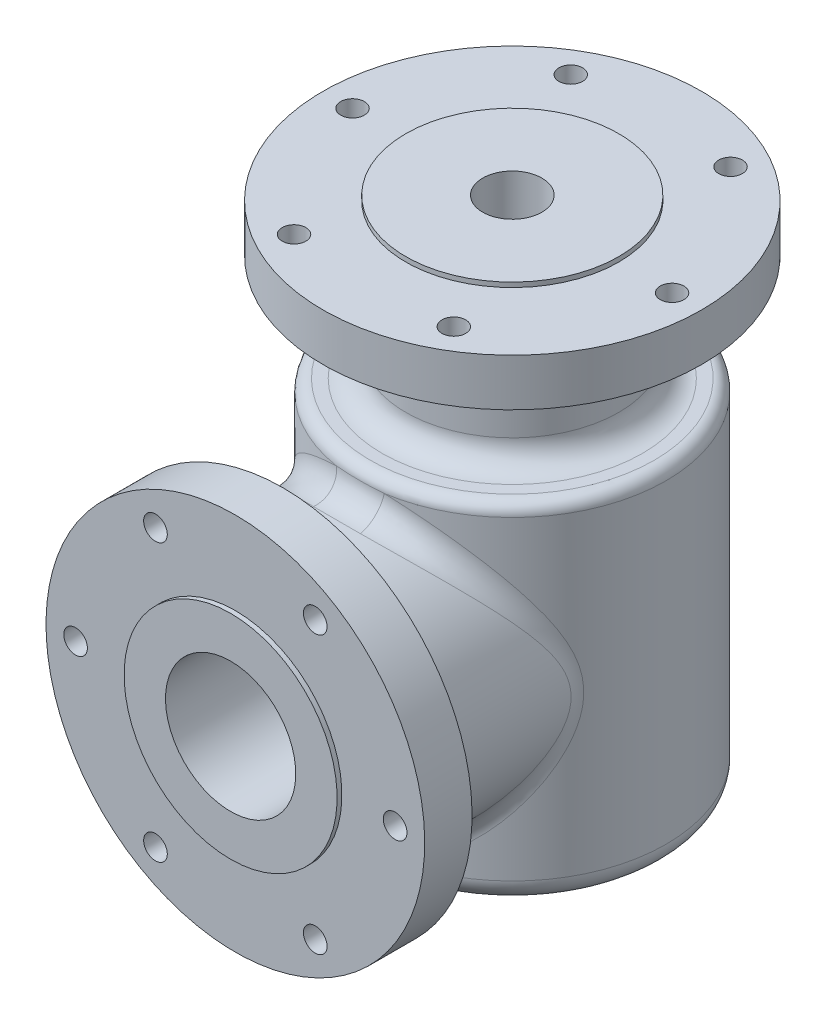
SolidWorks part; units mm, degrees
ref_plane "Front Plane" through (0, 0, 0) normal (0, 0, 1) x (1, 0, 0)
ref_plane "Top Plane" through (0, 0, 0) normal (0, 1, 0) x (1, 0, 0)
ref_plane "Right Plane" through (0, 0, 0) normal (1, 0, 0) x (0, 0, -1)
sketch "Sketch1" plane through (0, 0, 0) normal (0, 0, 1) x (1, 0, 0)
  line L0 (0, 0) -> (0, 259.5727) construction
  line L1 (21, 0) -> (55, 0)
  line L2 (65, 10) -> (65, 143)
  line L3 (60, 148) -> (55, 148)
  line L4 (45, 158) -> (45, 183)
  line L5 (55, 193) -> (80, 193)
  line L6 (80, 193) -> (80, 213)
  line L7 (80, 213) -> (45, 213)
  line L8 (45, 213) -> (45, 215)
  line L9 (45, 215) -> (12.5, 215)
  line L10 (15, 41.7864) -> (29, 41.7864)
  line L11 (43, 55.7864) -> (43, 115.7864)
  line L12 (29, 129.7864) -> (18, 129.7864)
  line L13 (12.5, 215) -> (12.5, 137.7864)
  line L14 (12.5, 137.7864) -> (18, 129.7864)
  line L15 (15, 41.7864) -> (15, 4)
  line L16 (15, 4) -> (21, 0)
  arc A0 (29, 41.7864) -> (43, 55.7864) centre (29, 55.7864) ccw
  arc A1 (43, 115.7864) -> (29, 129.7864) centre (29, 115.7864) ccw
  arc A2 (55, 148) -> (45, 158) centre (55, 158) cw
  arc A3 (45, 183) -> (55, 193) centre (55, 183) cw
  arc A4 (55, 0) -> (65, 10) centre (55, 10) ccw
  arc A5 (65, 143) -> (60, 148) centre (60, 143) ccw
  point P17 (0, 215)
  point P24 (43, 41.7864)
  point P27 (43, 129.7864)
  point P33 (65, 0)
  point P36 (65, 148)
  dimension "D18" = 14
  dimension "D19" = 10
  dimension "D20" = 10
  dimension "D21" = 5
  dimension "D1" = 65
  dimension "D2" = 215
  dimension "D3" = 148
  dimension "D4" = 88
  dimension "D5" = 21
  dimension "D6" = 43
  dimension "D7" = 2
  dimension "D8" = 15
  dimension "D9" = 4
  dimension "D10" = 37.7864
  dimension "D11" = 20
  dimension "D12" = 80
  dimension "D13" = 45
  dimension "D14" = 45
  dimension "D15" = 12.5
  dimension "D16" = 8
  dimension "D17" = 18
revolve "Revolve1" add sketch "Sketch1" angle 360 about L0
sketch "Sketch2" plane through (0, 0, 0) normal (1, 0, 0) x (0, 0, -1)
  line L0 (65, 76.5) -> (-119, 76.5) construction
  line L1 (65, 10) -> (65, 143) construction
  line L2 (-119, 104.0144) -> (-119, 121.5)
  line L3 (-119, 121.5) -> (-117, 121.5)
  line L4 (-117, 121.5) -> (-117, 156.5)
  line L5 (-117, 156.5) -> (-97, 156.5)
  line L6 (-97, 156.5) -> (-97, 134.0144)
  line L7 (-97, 134.0144) -> (-29.9513, 134.0144)
  line L8 (-29.9513, 134.0144) -> (-29.9513, 104.0144)
  line L9 (-119, 104.0144) -> (-29.9513, 104.0144)
  point P12 (-29.9513, 111.5)
  dimension "D1" = 45
  dimension "D2" = 80
  dimension "D3" = 2
  dimension "D4" = 20
  dimension "D5" = 57.5144
  dimension "D6" = 87.0487
  dimension "D7" = 30
  dimension "D8" = 94.9513
  dimension "D9" = 184
revolve "Revolve3" add sketch "Sketch2" angle 360 about L0
sketch "Sketch3" plane through (0, 0, 119) normal (0, 0, 1) x (1, 0, 0)
  circle A0 centre (0, 76.5) radius 27.5144
  dimension "D1" = 55.0287
extrude "Cut-Extrude1" cut sketch "Sketch3" against normal blind 119
fillet "Fillet1" radius 10 1 edges at (0, 134.0144, 97)
fillet "Fillet2" radius 10 1 edges at (5.3839, 19.2382, 64.7766)
sketch "Sketch4" plane through (0, 213, 0) normal (0, 1, 0) x (1, 0, 0)
  circle A0 centre (0, 0) radius 67.5 construction
  circle A1 centre (67.5, 0) radius 5
  circle A2 centre (33.75, -58.4567) radius 5
  circle A3 centre (-33.75, -58.4567) radius 5
  circle A4 centre (-67.5, 0) radius 5
  circle A5 centre (-33.75, 58.4567) radius 5
  circle A6 centre (33.75, 58.4567) radius 5
  point P18 (0, 0)
  dimension "D1" = 135
  dimension "D2" = 10
  dimension "D3" = 6
extrude "Cut-Extrude2" cut sketch "Sketch4" against normal blind 41
sketch "Sketch5" plane through (0, 0, 117) normal (0, 0, 1) x (1, 0, 0)
  line L0 (0, 76.5) -> (67.5, 76.5) construction
  circle A0 centre (0, 76.5) radius 67.5 construction
  circle A1 centre (67.5, 76.5) radius 5
  circle A2 centre (33.75, 18.0433) radius 5
  circle A3 centre (-33.75, 18.0433) radius 5
  circle A4 centre (-67.5, 76.5) radius 5
  circle A5 centre (-33.75, 134.9567) radius 5
  circle A6 centre (33.75, 134.9567) radius 5
  dimension "D1" = 135
  dimension "D2" = 10
  dimension "D3" = 6
  dimension "D4" = 67.5
extrude "Cut-Extrude3" cut sketch "Sketch5" against normal blind 41
